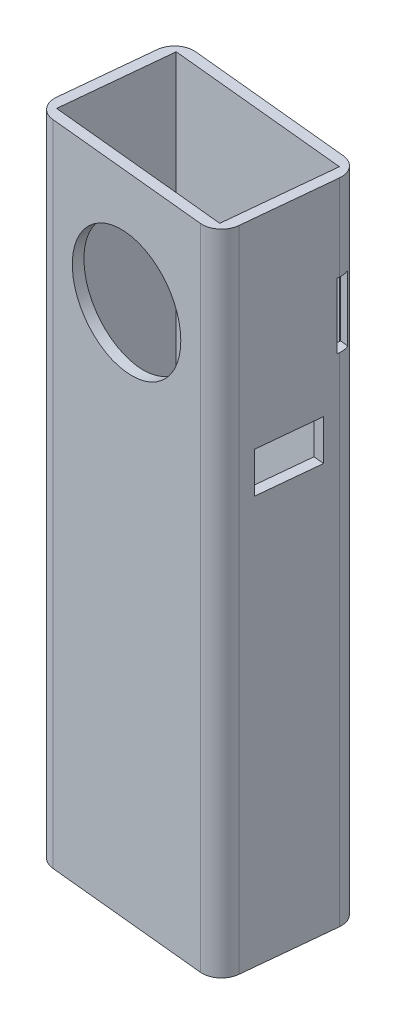
SolidWorks part; units mm, degrees
ref_plane "Front Plane" through (0, 0, 0) normal (0, 0, 1) x (1, 0, 0)
ref_plane "Top Plane" through (0, 0, 0) normal (0, 1, 0) x (1, 0, 0)
ref_plane "Right Plane" through (0, 0, 0) normal (1, 0, 0) x (0, 0, -1)
sketch "Sketch1" plane through (0, 0, 0) normal (0, 1, 0) x (1, 0, 0)
  line L0 (0, 0) -> (41.796, -4.135)
  line L1 (0, 0) -> (2.6582, 26.8688)
  line L2 (41.796, -4.135) -> (44.4542, 22.7338)
  line L3 (2.6582, 26.8688) -> (44.4542, 22.7338)
extrude "Boss-Extrude1" add sketch "Sketch1" along normal blind 130
shell "Shell1" thickness 2.2 removed face at (22.2271, 130, -11.3669)
sketch "Sketch3" plane through (41.796, 0, 4.135) normal (0.9951, 0, 0.0985) x (0.0985, 0, -0.9951)
  line L0 (13.5, 0) -> (13.5, 84.4446) construction
  line L1 (0, 0) -> (27, 0) construction
  line L2 (7, 80.2446) -> (20, 80.2446)
  line L3 (7, 80.2446) -> (7, 88.6446)
  line L4 (20, 80.2446) -> (20, 88.6446)
  line L5 (7, 88.6446) -> (20, 88.6446)
  line L6 (7, 80.2446) -> (20, 88.6446) construction
  line L7 (20, 80.2446) -> (7, 88.6446) construction
extrude "Cut-Extrude1" cut sketch "Sketch3" against normal up to surface (2.2 mm away) up to face at (40.9357, 66.1, -9.516)
sketch "Sketch4" plane through (0, 0, 0) normal (-0.0985, 0, 0.9951) x (0.9951, 0, 0.0985)
  line L0 (21, 0) -> (21, 130) construction
  line L1 (0, 0) -> (42, 0) construction
  line L2 (0, 130) -> (42, 130) construction
  circle A0 centre (21, 106.5377) radius 12.5
sketch "Sketch5" plane through (0, 130, 0) normal (0, 1, 0) x (1, 0, 0)
  line L0 (42.0483, 20.7611) -> (44.2573, 20.7436) construction
  line L2 (41.796, -4.135) -> (44.4542, 22.7338) construction
sketch "Sketch6" plane through (41.796, 0, 4.135) normal (0.9951, 0, 0.0985) x (0.0985, 0, -0.9951)
  line L0 (25.0186, 130) -> (25.0186, 0) construction
  line L1 (0, 130) -> (27, 130) construction
  line L2 (0, 0) -> (27, 0) construction
  line L3 (25.0186, 112.2553) -> (25.0186, 98.7283)
  line L4 (25.0186, 112.2553) -> (22.5397, 112.2553)
  line L5 (25.0186, 98.7283) -> (22.5397, 98.7283)
  line L6 (22.5397, 112.2553) -> (22.5397, 98.7283)
extrude "Cut-Extrude2" cut sketch "Sketch6" against normal up to surface (2.2 mm away) contours L4 L6 L5 L3 up to face at (40.9357, 84.4446, -9.516)
extrude "Cut-Extrude3" cut sketch "Sketch4" against normal up to surface (2.2 mm away) contours A0 up to face at (21.1146, 66.1, -0.1218)
fillet "Fillet1" radius 4 4 edges at (2.6582, 65, -26.8688) (44.4542, 65, -22.7338) (41.796, 65, 4.135) (0, 65, 0)
sketch "Sketch7" plane through (39.6066, 0, 3.9184) normal (-0.9951, 0, -0.0985) x (-0.0985, 0, 0.9951)
  line L0 (-2.2, 2.2) -> (-2.2, 52.5253)
  line L1 (-2.2, 130) -> (-2.2, 2.2) construction
  line L2 (-2.2, 52.5253) -> (-24.8, 52.5253)
  line L3 (-24.8, 98.7283) -> (-24.8, 2.2) construction
  line L4 (-24.8, 52.5253) -> (-24.8, 2.2)
  line L5 (-2.2, 2.2) -> (-24.8, 2.2)
extrude "Boss-Extrude2" add sketch "Sketch7" along normal blind 3
sketch "Sketch8" plane through (36.6212, 0, 3.623) normal (-0.9951, 0, -0.0985) x (-0.0985, 0, 0.9951)
  line L0 (-2.2, 2.2) -> (-2.2, 52.5253) construction
  line L1 (-2.2, 36.7574) -> (-24.8, 36.7574)
  line L2 (-2.2, 36.7574) -> (-2.2, 13.1853)
  line L3 (-2.2, 13.1853) -> (-24.8, 13.1853)
  line L4 (-24.8, 36.7574) -> (-24.8, 13.1853)
  line L5 (-24.8, 52.5253) -> (-24.8, 2.2) construction
extrude "Cut-Extrude4" cut sketch "Sketch8" against normal blind 3
chamfer "Chamfer1" distance 10 angle 29 1 edges at (37.9503, 36.7574, -9.8114) first distance on face at (37.9503, 44.6414, -9.8114)
sketch "Sketch9" plane through (0, 0, 0) normal (0, -1, 0) x (1, 0, 0)
  line L0 (6.6388, -26.475) -> (40.4736, -23.1277)
  line L1 (2.2644, -22.8883) -> (0.3938, -3.9806)
  line L2 (44.0604, -18.7533) -> (42.1898, 0.1544)
  line L3 (3.9806, 0.3938) -> (37.8154, 3.7412)
  arc A0 (6.6388, -26.475) -> (2.2644, -22.8883) centre (6.245, -22.4945) cw
  arc A1 (0.3938, -3.9806) -> (3.9806, 0.3938) centre (4.3744, -3.5868) cw
  arc A2 (37.8154, 3.7412) -> (42.1898, 0.1544) centre (38.2092, -0.2394) cw
  arc A3 (44.0604, -18.7533) -> (40.4736, -23.1277) centre (40.0798, -19.1471) cw
extrude "Boss-Extrude3" add sketch "Sketch9" along normal blind 4
sketch "Sketch11" plane through (0, -4, 0) normal (0, -1, 0) x (1, 0, 0)
  line L0 (26.1151, -16.5627) -> (28.8479, -10.7023)
  line L1 (22.7704, -16.8554) -> (26.1151, -16.5627)
  line L2 (22.7704, -16.8554) -> (19.4256, -17.148)
  line L3 (19.4256, -17.148) -> (15.7166, -11.8511)
  line L4 (18.4494, -5.9906) -> (15.7166, -11.8511)
  line L5 (25.139, -5.4054) -> (28.8479, -10.7023)
  line L6 (21.7942, -5.698) -> (25.139, -5.4054)
  line L7 (21.7942, -5.698) -> (18.4494, -5.9906)
  line L8 (20.898, 2.0675) -> (23.5562, -24.8013) construction
  line L9 (37.8154, 3.7412) -> (3.9806, 0.3938) construction
  line L10 (6.6388, -26.475) -> (40.4736, -23.1277) construction
  line L11 (43.1251, -9.2994) -> (1.3291, -13.4344) construction
  line L12 (44.0604, -18.7533) -> (42.1898, 0.1544) construction
  line L13 (0.3938, -3.9806) -> (2.2644, -22.8883) construction
extrude "Cut-Extrude5" cut sketch "Sketch11" against normal blind 5
